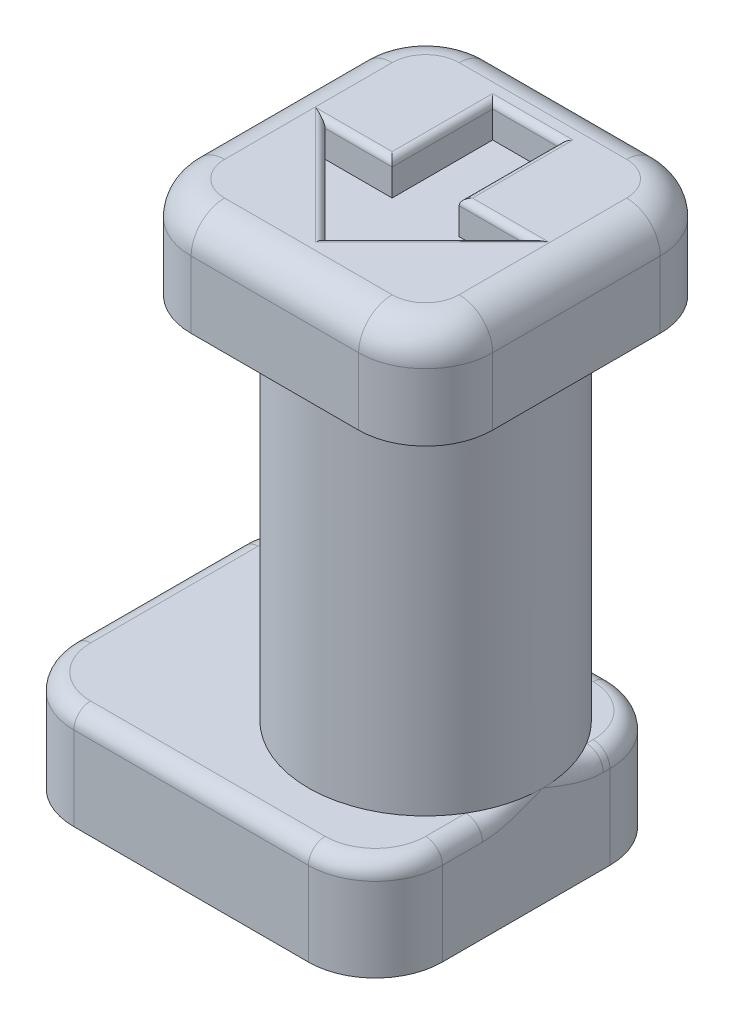
SolidWorks part; units mm, degrees
ref_plane "Спереди" through (0, 0, 0) normal (0, 0, 1) x (1, 0, 0)
ref_plane "Сверху" through (0, 0, 0) normal (0, 1, 0) x (1, 0, 0)
ref_plane "Справа" through (0, 0, 0) normal (1, 0, 0) x (0, 0, -1)
sketch "Эскиз1" plane through (0, 0, 0) normal (0, 1, 0) x (1, 0, 0)
  line L2 (4.5, -2.5) -> (4.5, 2.5)
  line L3 (-4.5, -2.5) -> (-4.5, 2.5)
  line L4 (-2.5, -4.5) -> (2.5, -4.5)
  line L5 (-2.5, 4.5) -> (2.5, 4.5)
  arc A0 (-4.5, -2.5) -> (-2.5, -4.5) centre (-2.5, -2.5) ccw
  arc A1 (2.5, -4.5) -> (4.5, -2.5) centre (2.5, -2.5) ccw
  arc A2 (4.5, 2.5) -> (2.5, 4.5) centre (2.5, 2.5) ccw
  arc A3 (-4.5, 2.5) -> (-2.5, 4.5) centre (-2.5, 2.5) cw
  point P4 (4.5, -1000)
  point P6 (4.5, 49000)
  point P7 (-4.5, -1000)
  point P8 (-4.5, 49000)
  point P9 (-1000, -4.5)
  point P10 (49000, -4.5)
  point P11 (-1000, 4.5)
  point P12 (49000, 4.5)
  dimension "D1" = 2
extrude "Бобышка-Вытянуть1" add sketch "Эскиз1" along normal blind 3
fillet "Скругление1" radius 1 8 edges at (3.9142, 3, -3.9142) (4.5, 3, 0) (3.9142, 3, 3.9142) (0, 3, 4.5) (-3.9142, 3, 3.9142) (-4.5, 3, 0) (-3.9142, 3, -3.9142) (0, 3, -4.5)
sketch "Эскиз2" plane through (0, 0, 0) normal (0, -1, 0) x (1, 0, 0)
  circle A0 centre (0, 0) radius 3.5
extrude "Бобышка-Вытянуть2" add sketch "Эскиз2" along normal blind 16
sketch "Эскиз3" plane through (0, 3, 0) normal (0, 1, 0) x (1, 0, 0)
  line L0 (-1003.5, -2.5) -> (48996.5, -2.5) construction
  line L1 (-1003.5, 2.5) -> (48996.5, 2.5) construction
  line L2 (0, -1000) -> (0, 49000) construction
  line L6 (-1003.5, 0.5) -> (48996.5, 0.5) construction
  line L7 (0, -3) -> (-3, 0)
  line L8 (0, -3) -> (3, 0)
  line L9 (-1003.5, 3) -> (48996.5, 3) construction
  line L16 (-1003.5, -3) -> (48996.5, -3) construction
  line L20 (-1003.5, 0) -> (48996.5, 0) construction
  line L25 (-1, -1000) -> (-1, 49000) construction
  line L26 (1, -1000) -> (1, 49000) construction
  line L27 (-1, 0) -> (-1, 2.5)
  line L29 (1, 2.5) -> (1, 0)
  line L30 (1, 0) -> (3, 0)
  line L31 (-1, 0) -> (-3, 0)
  line L32 (-1, 2.5) -> (-1, 3)
  line L33 (-1, 3) -> (1, 3)
  line L34 (1, 3) -> (1, 2.5)
  point P7 (1, -1000)
  point P10 (1, 49000)
  point P11 (-1, -1000)
  point P12 (-1, 49000)
  dimension "D2" = 0.5
  dimension "D1" = 0.5
extrude "Вырез-Вытянуть1" cut sketch "Эскиз3" against normal blind 1
fillet "Скругление2" radius 0.2 7 edges at (1.5, 3, 1.5) (2, 3, 0) (0, 3, -3) (1, 3, -1.5) (-1, 3, -1.5) (-2, 3, 0) (-1.5, 3, 1.5)
sketch "Эскиз6" plane through (0, -16, 0) normal (0, -1, 0) x (1, 0, 0)
  line L0 (-1000, 0) -> (49000, 0) construction
  line L1 (0, -1000) -> (0, 49000) construction
  line L2 (-2, -1000) -> (-2, 49000) construction
  line L3 (-1000, 1) -> (49000, 1) construction
  circle A3 centre (-2, 0) radius 3.75
  dimension "D1" = 1
sketch "Эскиз7" plane through (0, -16, 0) normal (0, -1, 0) x (1, 0, 0)
  line L0 (-1000, -3.5) -> (49000, -3.5) construction
  line L1 (-5.5, -4) -> (1.5, -4)
  line L2 (3.5, -1000) -> (3.5, 49000) construction
  line L4 (-7.5, -994.5) -> (-7.5, 49005.5) construction
  line L5 (-1002, 5) -> (48998, 5) construction
  line L6 (-5.5, -998) -> (-5.5, 49002) construction
  line L7 (-7.5, 3) -> (-7.5, -2)
  line L11 (3.5, 3) -> (3.5, -2)
  line L12 (-5.5, 5) -> (1.5, 5)
  line L14 (-1007.5, -2) -> (48992.5, -2) construction
  line L15 (-1002, 3) -> (48998, 3) construction
  arc A1 (-5.5, -4) -> (-7.5, -2) centre (-5.5, -2) cw
  arc A2 (3.5, -2) -> (1.5, -4) centre (1.5, -2) cw
  arc A4 (-5.5, 5) -> (-7.5, 3) centre (-5.5, 3) ccw
  arc A5 (1.5, 5) -> (3.5, 3) centre (1.5, 3) cw
  point P7 (-1002, 7.5)
  point P9 (48998, 7.5)
  point P10 (-7.5, -998)
  point P11 (-7.5, 49002)
  point P21 (3.5, -3.5)
  point P24 (3.5, 7.5)
  dimension "D2" = 2
extrude "Бобышка-Вытянуть3" add sketch "Эскиз7" against normal blind 5
extrude "Вырез-Вытянуть2" cut sketch "Эскиз6" against normal blind 4
fillet "Скругление3" radius 0.5 9 edges at (3.5, -11, -1) (3.5, -11, 1.5) (2.9142, -11, -3.4142) (-2, -11, -4) (-6.9142, -11, -3.4142) (-7.5, -11, 0.5) (-6.9142, -11, 4.4142) (-2, -11, 5) (2.9142, -11, 4.4142)
sketch "Эскиз8" plane through (0, -16, 0) normal (0, -1, 0) x (1, 0, 0)
  line L1 (4.6164, 8.2931) -> (-8.6164, 8.2931)
  line L2 (4.6164, 8.2931) -> (4.6164, -4.2931)
  line L3 (4.6164, -4.2931) -> (-8.6164, -4.2931)
  line L4 (-8.6164, 8.2931) -> (-8.6164, -4.2931)
  line L5 (4.6164, 8.2931) -> (-8.6164, -4.2931) construction
  line L6 (4.6164, -4.2931) -> (-8.6164, 8.2931) construction
  point P0 (-2, 2)
extrude "Вырез-Вытянуть3" cut sketch "Эскиз8" against normal blind 2
